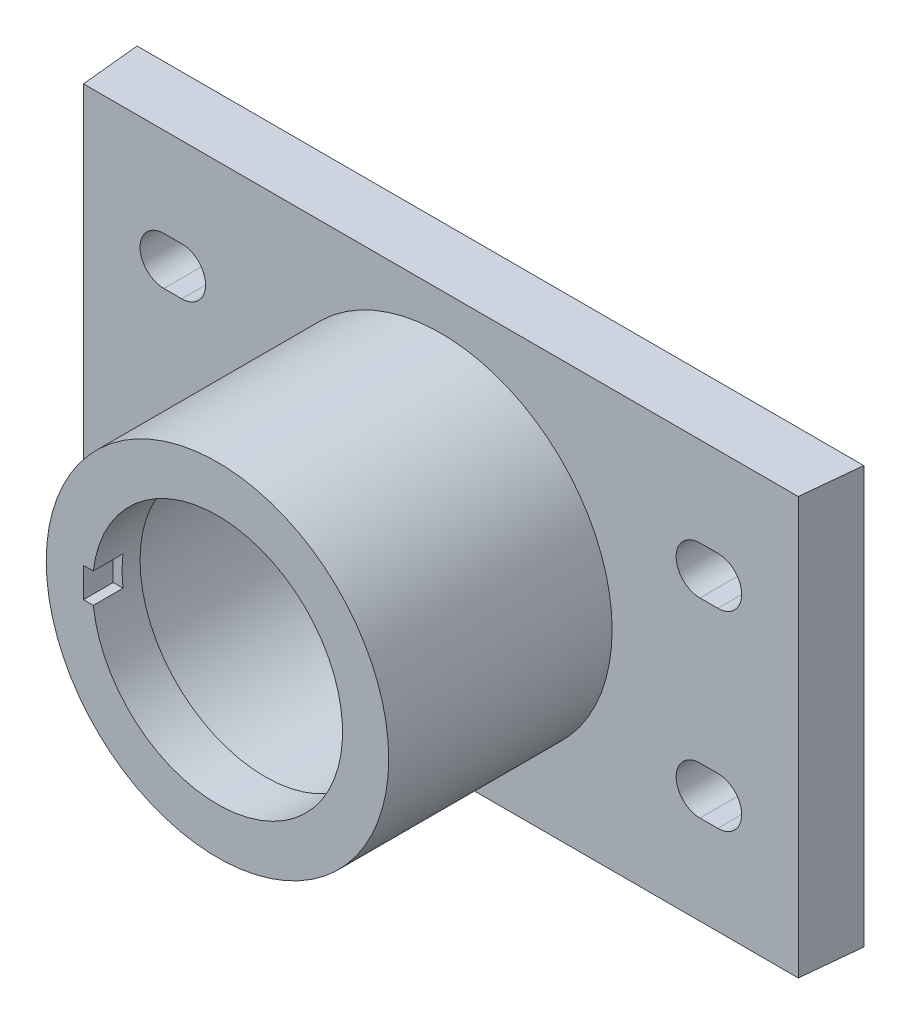
SolidWorks part; units mm, degrees
ref_plane "Front Plane" through (0, 0, 0) normal (0, 0, 1) x (1, 0, 0)
ref_plane "Top Plane" through (0, 0, 0) normal (0, 1, 0) x (1, 0, 0)
ref_plane "Right Plane" through (0, 0, 0) normal (1, 0, 0) x (0, 0, -1)
sketch "Sketch1" plane through (0, 0, 0) normal (0, 0, 1) x (1, 0, 0)
  line L1 (-120, -70) -> (120, -70)
  line L2 (-120, -70) -> (-120, 70)
  line L3 (-120, 70) -> (120, 70)
  line L4 (120, -70) -> (120, 70)
  line L5 (-120, -70) -> (120, 70) construction
  line L6 (-120, 70) -> (120, -70) construction
  point P0 (0, 0)
  dimension "D1" = 240
  dimension "D2" = 140
extrude "Boss-Extrude2" add sketch "Sketch1" along normal blind 20
draft "Draft1" type of draft neutral plane draft angle 5.7 faces to draft 2 face at (120, 0, 10) face at (-120, 0, 10) neutral plane through (0, 0, 20) neutral plane normal (0, 0, 1) parameters "D1"=5.7
sketch "Sketch4" plane through (0, 0, 0) normal (0, 0, -1) x (-1, 0, 0)
  line L2 (121.9963, -70) -> (-121.9963, -70) construction
  line L6 (-102.9963, -51) -> (-12, -51)
  line L7 (-12, 50.6074) -> (-12, -51)
  line L12 (-12, 50.6074) -> (-102.9963, 50.6074)
  line L14 (12, 50.6074) -> (12, -51)
  line L15 (-102.9963, 50.6074) -> (-102.9963, -51)
  line L16 (102.9963, -51) -> (12, -51)
  line L17 (102.9963, 50.6074) -> (102.9963, -51)
  line L18 (12, 50.6074) -> (102.9963, 50.6074)
  dimension "D7" = 19
extrude "Cut-Extrude1" cut sketch "Sketch4" against normal blind 2 contours L7 L6 L15 L12 | L14 L16 L17 L18
sketch "Sketch5" plane through (0, 0, 0) normal (0, 0, -1) x (-1, 0, 0)
  line L5 (-92.9963, 24) -> (-86.9963, 24)
  line L7 (-92.9963, 40) -> (-86.9963, 40)
  arc A0 (-92.9963, 24) -> (-92.9963, 40) centre (-92.9963, 32) cw
  arc A1 (-86.9963, 24) -> (-86.9963, 40) centre (-86.9963, 32) ccw
  point P8 (-89.9963, 32)
extrude "Cut-Extrude3" cut sketch "Sketch5" against normal blind 52
mirror "Mirror1" about plane through (0, 0, 0) normal (1, 0, 0) of "Cut-Extrude3"
mirror "Mirror2" about plane through (0, 0, 0) normal (0, 1, 0) of "Mirror1"
sketch "Sketch6" plane through (0, 0, 20) normal (0, 0, 1) x (1, 0, 0)
  circle A0 centre (0, 0) radius 57.5
  circle A1 centre (0, 0) radius 42
extrude "Boss-Extrude3" add sketch "Sketch6" along normal blind 75
sketch "Sketch7" plane through (0, 0, 95) normal (0, 0, 1) x (1, 0, 0)
  line L1 (-45, -5) -> (-39, -5)
  line L2 (-45, -5) -> (-45, 5)
  line L3 (-45, 5) -> (-39, 5)
  line L4 (-39, -5) -> (-39, 5)
  line L5 (-45, -5) -> (-39, 5) construction
  line L6 (-45, 5) -> (-39, -5) construction
  circle A0 centre (0, 0) radius 42 construction
  circle A1 centre (0, 0) radius 42 construction
  point P0 (-42, 0)
  point P9 (0, 0)
  dimension "D1" = 10
  dimension "D2" = 6
extrude "Cut-Extrude4" cut sketch "Sketch7" against normal blind 10
sketch "Sketch8" plane through (0, 0, 0) normal (0, 1, 0) x (1, 0, 0)
  line L1 (-42, -34) -> (-44, -34)
  line L3 (-42, -79) -> (-44, -79)
  line L4 (-44, -34) -> (-44, -79)
  line L5 (-42, -79) -> (-42, -34)
  line L6 (-42, -20) -> (42, -20) construction
  line L7 (0, 0) -> (0, -119.8514)
  dimension "D1" = 14
  dimension "D2" = 45
  dimension "D3" = 2
revolve "Cut-Revolve1" cut sketch "Sketch8" angle 360 about L7
